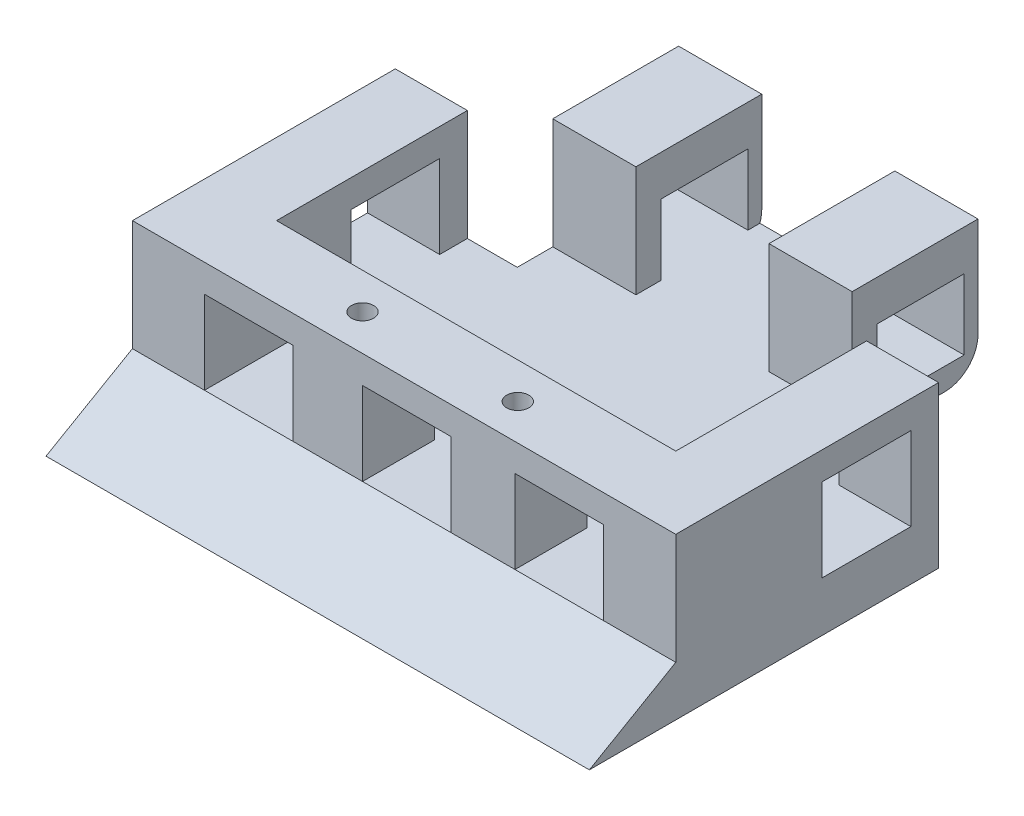
SolidWorks part; units mm, degrees
ref_plane "Alzado" through (0, 0, 0) normal (0, 0, 1) x (1, 0, 0)
ref_plane "Planta" through (0, 0, 0) normal (0, 1, 0) x (1, 0, 0)
ref_plane "Vista lateral" through (0, 0, 0) normal (1, 0, 0) x (0, 0, -1)
sketch "Croquis1" plane through (0, 0, 0) normal (0, 1, 0) x (1, 0, 0)
  line L1 (-49, -49) -> (49, -49)
  line L2 (-49, -49) -> (-49, 49)
  line L3 (-49, 49) -> (49, 49)
  line L4 (49, -49) -> (49, 49)
  line L5 (-49, -49) -> (49, 49) construction
  line L6 (-49, 49) -> (49, -49) construction
  point P0 (0, 0)
  dimension "D1" = 98
  dimension "D2" = 98
extrude "Saliente-Extruir1" add sketch "Croquis1" along normal blind 9
chamfer "Chaflán1" distance 9 angle 60 1 edges at (0, 9, 49) first distance on face at (0, 4.5, 49)
sketch "Croquis2" plane through (0, 9, 0) normal (0, 1, 0) x (1, 0, 0)
  line L5 (-49, 49) -> (-27, 49)
  line L6 (-49, 49) -> (-49, 14)
  line L7 (-49, 14) -> (-27, 14)
  line L8 (-27, 49) -> (-27, 14)
  line L9 (49, 49) -> (27, 49)
  line L10 (49, 49) -> (49, 14)
  line L11 (49, 14) -> (27, 14)
  line L12 (27, 49) -> (27, 14)
  dimension "D1" = 22
  dimension "D2" = 35
  dimension "D3" = 22
  dimension "D4" = 35
extrude "Cortar-Extruir1" cut sketch "Croquis2" against normal blind 9
sketch "Croquis3" plane through (0, 9, 0) normal (0, 1, 0) x (1, 0, 0)
  line L0 (27, 49) -> (27, 14) construction
  line L1 (27, 40.6) -> (12, 40.6)
  line L3 (27, 25.4) -> (12, 25.4)
  line L5 (-27, 14) -> (-27, 49) construction
  line L6 (-27, 40.6) -> (-12, 40.6)
  line L8 (-27, 25.4) -> (-12, 25.4)
  line L17 (-27, 22.9) -> (-12, 22.9)
  line L19 (-27, 43.1) -> (-12, 43.1)
  line L20 (-27, 40.6) -> (-27, 43.1)
  line L21 (-27, 25.4) -> (-27, 22.9)
  line L22 (-29.5, 22.9) -> (-9.5, 22.9) construction
  line L23 (-29.5, 43.1) -> (-29.5, 22.9) construction
  line L24 (-29.5, 43.1) -> (-9.5, 43.1) construction
  line L25 (-27, 40.6) -> (-27, 25.4) construction
  line L26 (-12, 40.6) -> (-12, 25.4) construction
  line L27 (-9.5, 43.1) -> (-9.5, 22.9) construction
  line L28 (-12, 40.6) -> (-12, 43.1)
  line L29 (-12, 25.4) -> (-12, 22.9)
  line L31 (27, 22.9) -> (12, 22.9)
  line L33 (27, 43.1) -> (12, 43.1)
  line L34 (9.5, 43.1) -> (9.5, 22.9) construction
  line L35 (12, 40.6) -> (12, 25.4) construction
  line L36 (27, 40.6) -> (27, 25.4) construction
  line L37 (29.5, 43.1) -> (29.5, 22.9) construction
  line L38 (27, 40.6) -> (27, 43.1)
  line L39 (12, 40.6) -> (12, 43.1)
  line L40 (12, 25.4) -> (12, 22.9)
  line L41 (27, 25.4) -> (27, 22.9)
  line L42 (29.5, 43.1) -> (9.5, 43.1) construction
  line L43 (29.5, 22.9) -> (9.5, 22.9) construction
  dimension "D1" = 15.2
  dimension "D3" = 15
  dimension "D4" = 15.2
  dimension "D5" = 15
  dimension "D6" = 2.5
  dimension "D7" = 2.5
extrude "Saliente-Extruir2" add sketch "Croquis3" along normal blind 12.2
sketch "Croquis4" plane through (0, 21.2, 0) normal (0, 1, 0) x (1, 0, 0)
  line L1 (-27, 22.9) -> (-12, 22.9)
  line L2 (-27, 22.9) -> (-27, 43.1)
  line L3 (-27, 43.1) -> (-12, 43.1)
  line L4 (-12, 22.9) -> (-12, 43.1)
  line L5 (12, 43.1) -> (27, 43.1)
  line L6 (12, 43.1) -> (12, 22.9)
  line L7 (12, 22.9) -> (27, 22.9)
  line L8 (27, 43.1) -> (27, 22.9)
extrude "Saliente-Extruir3" add sketch "Croquis4" along normal blind 2.5
sketch "Croquis5" plane through (27, 0, 0) normal (1, 0, 0) x (0, 0, -1)
  line L1 (43.1, 9) -> (49, 9)
  line L2 (43.1, 9) -> (43.1, 0)
  line L3 (43.1, 0) -> (49, 0)
  line L4 (49, 9) -> (49, 0)
extrude "Cortar-Extruir2" cut sketch "Croquis5" against normal blind 54.2
sketch "Croquis6" plane through (0, 0, -22.9) normal (0, 0, 1) x (1, 0, 0)
  line L1 (-27, 23.7) -> (-12, 23.7)
  line L2 (-27, 23.7) -> (-27, 9)
  line L3 (-27, 9) -> (-12, 9)
  line L4 (-12, 23.7) -> (-12, 9)
  line L5 (12, 23.7) -> (27, 23.7)
  line L6 (12, 23.7) -> (12, 9)
  line L7 (12, 9) -> (27, 9)
  line L8 (27, 23.7) -> (27, 9)
extrude "Saliente-Extruir4" add sketch "Croquis6" along normal blind 2.5
sketch "Croquis7" plane through (0, 9, 0) normal (0, 1, 0) x (1, 0, 0)
  line L0 (-49, 14) -> (-49, -33.4115)
  line L1 (-49, -33.4115) -> (49, -33.4115)
  line L2 (49, -33.4115) -> (49, 14)
  line L3 (-36, 14) -> (-36, -20.4115)
  line L4 (-36, -20.4115) -> (36, -20.4115)
  line L5 (36, -20.4115) -> (36, 14)
  line L6 (49, 14) -> (36, 14)
  line L7 (-36, 14) -> (-49, 14)
  dimension "D1" = 13
extrude "Saliente-Extruir5" add sketch "Croquis7" along normal blind 20
sketch "Croquis8" plane through (49, 0, 0) normal (1, 0, 0) x (0, 0, -1)
  line L0 (20.4, 9) -> (14, 9) construction
  line L1 (-7, 9) -> (9, 9)
  line L2 (-7, 9) -> (-7, 24)
  line L3 (-7, 24) -> (9, 24)
  line L4 (9, 9) -> (9, 24)
  line L5 (14, 0) -> (14, 29) construction
  dimension "D1" = 16
  dimension "D2" = 15
  dimension "D3" = 5
extrude "Cortar-Extruir3" cut sketch "Croquis8" against normal blind 98
sketch "Croquis9" plane through (0, 0, 33.4115) normal (0, 0, 1) x (1, 0, 0)
  line L0 (-49, 9) -> (49, 9) construction
  line L1 (-36, 9) -> (-20, 9)
  line L2 (-36, 9) -> (-36, 24)
  line L3 (-36, 24) -> (-20, 24)
  line L4 (-20, 9) -> (-20, 24)
  line L5 (49, 29) -> (49, 9) construction
  line L6 (-7.5, 9) -> (8.5, 9)
  line L7 (-7.5, 9) -> (-7.5, 24)
  line L8 (-7.5, 24) -> (8.5, 24)
  line L9 (8.5, 9) -> (8.5, 24)
  line L10 (20, 9) -> (36, 9)
  line L11 (20, 9) -> (20, 24)
  line L12 (20, 24) -> (36, 24)
  line L13 (36, 9) -> (36, 24)
  line L14 (-49, 29) -> (-49, 9) construction
  point P18 (0.5, 24)
  dimension "D1" = 13
  dimension "D2" = 13
  dimension "D3" = 16
  dimension "D4" = 16
  dimension "D5" = 16
  dimension "D6" = 20.5
  dimension "D7" = 15
  dimension "D8" = 15
  dimension "D9" = 15
extrude "Cortar-Extruir4" cut sketch "Croquis9" against normal blind 13
sketch "Croquis10" plane through (0, 23.7, 0) normal (0, 1, 0) x (1, 0, 0)
  line L1 (-27, 43.1) -> (-12, 43.1)
  line L2 (-27, 43.1) -> (-27, 20.4)
  line L3 (-27, 20.4) -> (-12, 20.4)
  line L4 (-12, 43.1) -> (-12, 20.4)
  line L5 (12, 43.1) -> (27, 43.1)
  line L6 (12, 43.1) -> (12, 20.4)
  line L7 (12, 20.4) -> (27, 20.4)
  line L8 (27, 43.1) -> (27, 20.4)
extrude "Saliente-Extruir6" add sketch "Croquis10" along normal blind 5.3
sketch "Croquis11" plane through (0, 29, 0) normal (0, 1, 0) x (1, 0, 0)
  line L6 (-49, 14) -> (-49, -33.4115) construction
  line L7 (49, -33.4115) -> (49, 14) construction
  line L9 (-36, -33.4115) -> (36, -33.4115) construction
  line L12 (36, -20.4115) -> (-36, -20.4115) construction
  circle A0 centre (-14, -26.9115) radius 2
  circle A1 centre (14, -26.9115) radius 2
  dimension "D5" = 4
  dimension "D6" = 4
  dimension "D7" = 6.5
  dimension "D8" = 6.5
  dimension "D9" = 35
  dimension "D10" = 35
  dimension "D3" = 13
  dimension "D4" = 13
extrude "Cortar-Extruir5" cut sketch "Croquis11" against normal blind 10
sketch "Croquis12" plane through (27, 0, 0) normal (1, 0, 0) x (0, 0, -1)
  line L1 (43.1, 0) -> (14, 0)
  line L2 (43.1, 0) -> (43.1, 5)
  line L3 (43.1, 5) -> (14, 5)
  line L4 (14, 0) -> (14, 5)
  line L5 (40.6, 9) -> (25.4, 9) construction
  point P7 (0, 0)
  dimension "D1" = 4
extrude "Cortar-Extruir6" cut sketch "Croquis12" against normal through all
sketch "Croquis13" plane through (0, 0, 0) normal (1, 0, 0) x (0, 0, -1)
  line L0 (19, 5) -> (14, 0)
  line L1 (43.1, 5) -> (14, 5) construction
  line L3 (14, 0) -> (14, 29) construction
  point P4 (0, 0)
  point P5 (14, 0)
  point P6 (0, 0)
  point P8 (0, 0)
  point P10 (18.362, 5)
  dimension "D1" = 45
rib "Nervio1" sketch "Croquis13" sketch "Croquis13" thickness 54 extrusion direction parallel to sketch draft on no parameters "D1"=54
fillet "Redondeo1" radius 6 1 edges at (0, 5, -43.1)
sketch "Croquis14" plane through (27, 0, 0) normal (1, 0, 0) x (0, 0, -1)
  line L0 (25.4, 21.2) -> (40.6, 21.2) construction
  line L1 (40.6, 9) -> (24.9, 9)
  line L2 (40.6, 9) -> (40.6, 21.7)
  line L3 (40.6, 21.7) -> (24.9, 21.7)
  line L4 (24.9, 9) -> (24.9, 21.7)
  line L5 (25.4, 21.2) -> (25.4, 9) construction
  dimension "D1" = 0.5
  dimension "D2" = 0.5
extrude "Cortar-Extruir7" cut sketch "Croquis14" against normal through all
